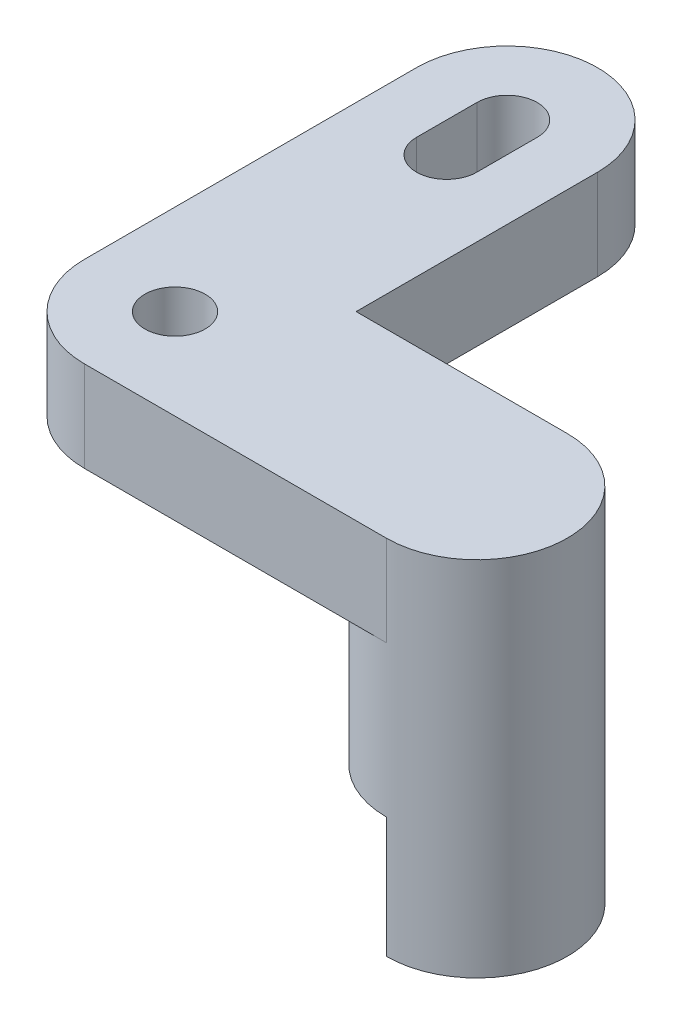
SolidWorks part; units mm, degrees
ref_plane "Front Plane" through (0, 0, 0) normal (0, 0, 1) x (1, 0, 0)
ref_plane "Top Plane" through (0, 0, 0) normal (0, 1, 0) x (1, 0, 0)
ref_plane "Right Plane" through (0, 0, 0) normal (1, 0, 0) x (0, 0, -1)
sketch "Sketch1" plane through (0, 0, 0) normal (0, 1, 0) x (1, 0, 0)
  line L0 (5, -1) -> (1.5, -1)
  line L2 (-1.5, 2.5) -> (-1.5, -2.5)
  line L4 (1.5, 2.5) -> (1.5, -1)
  line L5 (-1.5, 2.5) -> (1.5, -2.5) construction
  line L6 (-1.5, -2.5) -> (1.5, 2.5) construction
  line L7 (5, -4) -> (0, -4)
  line L8 (5, -1) -> (0, -4) construction
  line L9 (0, -1) -> (5, -4) construction
  line L10 (0, -2.5) -> (1.5, -2.5) construction
  line L11 (0, -2.5) -> (0, -4) construction
  line L12 (-0.5, 3) -> (-0.5, 2)
  line L13 (0.5, 3) -> (0.5, 2)
  line L14 (-1.5, 2.5) -> (-1.5, 3)
  line L15 (1.5, 3) -> (1.5, 2.5)
  arc A1 (-1.5, -2.5) -> (0, -4) centre (0, -2.5) ccw
  circle A2 centre (0, -2.5) radius 0.5
  arc A4 (5, -4) -> (5, -1) centre (5, -2.5) ccw
  arc A8 (0.5, 3) -> (-0.5, 3) centre (0, 3) ccw
  arc A9 (-0.5, 2) -> (0.5, 2) centre (0, 2) ccw
  arc A10 (1.5, 3) -> (-1.5, 3) centre (0, 3) ccw
  point P0 (0, 0)
  point P12 (2.5, -2.5)
  dimension "D3" = 1
  dimension "D1" = 3
  dimension "D2" = 5
  dimension "D6" = 90
  dimension "D5" = 2
extrude "Boss-Extrude1" add sketch "Sketch1" along normal blind 1.5
sketch "Sketch2" plane through (0, 1.5, 0) normal (0, 1, 0) x (1, 0, 0)
  circle A0 centre (5, -2.5) radius 1.5
  dimension "D1" = 3
extrude "Boss-Extrude2" add sketch "Sketch2" along normal blind 12
sketch "Sketch3" plane through (0, 13.5, 0) normal (0, 1, 0) x (1, 0, 0)
  line L0 (1.5, -1) -> (5, -1)
  line L1 (5, -4) -> (0, -4)
  line L2 (-1.5, -2.5) -> (-1.5, 2.5)
  line L3 (1.5, 2.5) -> (1.5, -1)
  line L4 (-0.5, 3) -> (-0.5, 2)
  line L5 (0.5, 3) -> (0.5, 2)
  line L6 (-1.5, 3) -> (-1.5, 2.5)
  line L7 (1.5, 3) -> (1.5, 2.5)
  arc A0 (5, -1) -> (5, -4) centre (5, -2.5) cw
  arc A1 (0, -4) -> (-1.5, -2.5) centre (0, -2.5) cw
  circle A4 centre (0, -2.5) radius 0.5
  arc A5 (0.5, 3) -> (-0.5, 3) centre (0, 3) ccw
  arc A6 (-0.5, 2) -> (0.5, 2) centre (0, 2) ccw
  arc A7 (1.5, 3) -> (-1.5, 3) centre (0, 3) ccw
extrude "Boss-Extrude3" add sketch "Sketch3" along normal blind 1.5
sketch "Sketch4" plane through (0, 0, 0) normal (0, -1, 0) x (1, 0, 0)
  line L1 (-4.5237, 5.3717) -> (7.8358, 5.3717)
  line L2 (-4.5237, 5.3717) -> (-4.5237, -5.3544)
  line L3 (-4.5237, -5.3544) -> (7.8358, -5.3544)
  line L4 (7.8358, 5.3717) -> (7.8358, -5.3544)
extrude "Cut-Extrude1" cut sketch "Sketch4" against normal blind 9
sketch "Sketch5" plane through (0, 9, 0) normal (0, -1, 0) x (1, 0, 0)
  line L0 (5, 1) -> (1.5, 1) construction
  line L1 (5, 4) -> (5, 1)
  arc A0 (5, 4) -> (5, 1) centre (5, 2.5) ccw
  circle A1 centre (5, 2.5) radius 1.5 construction
extrude "Cut-Extrude3" cut sketch "Sketch5" against normal blind 2
